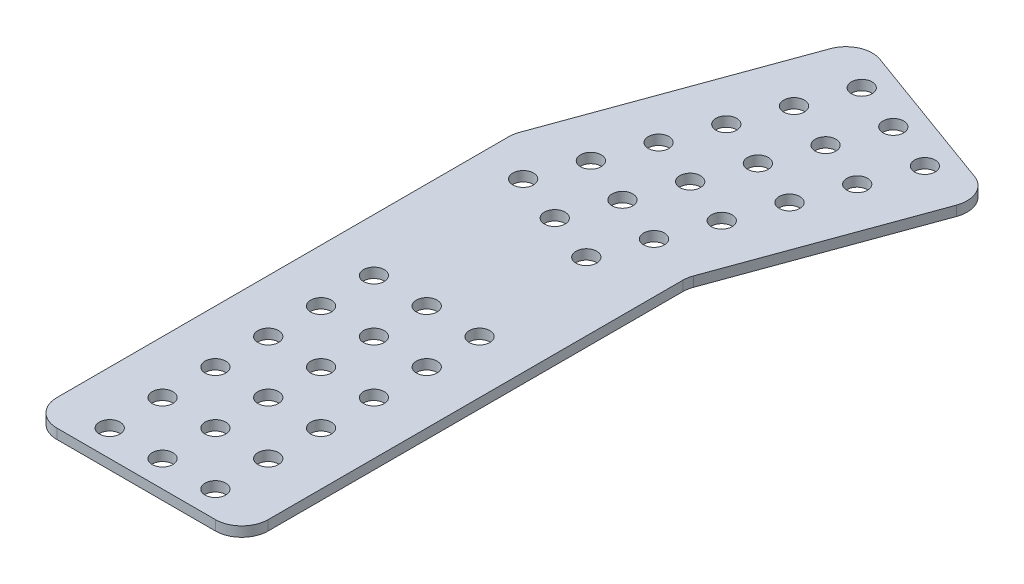
SolidWorks part; units mm, degrees
ref_plane "Front Plane" through (0, 0, 0) normal (0, 0, 1) x (1, 0, 0)
ref_plane "Top Plane" through (0, 0, 0) normal (0, 1, 0) x (1, 0, 0)
ref_plane "Right Plane" through (0, 0, 0) normal (1, 0, 0) x (0, 0, -1)
sketch "Sketch1" plane through (0, 0, 0) normal (0, 1, 0) x (1, 0, 0)
  line L0 (-80.3795, -295.1056) -> (-128.1159, -277.731) construction
  line L1 (-80.3795, -295.1056) -> (128.1159, 277.731) construction
  line L2 (-124.5455, -267.9214) -> (80.3795, 295.1056) construction
  line L3 (128.1159, 277.731) -> (80.3795, 295.1056) construction
  line L4 (-80.3795, -295.1056) -> (80.3795, 295.1056) construction
  line L5 (-128.1159, -277.731) -> (128.1159, 277.731) construction
  line L6 (104.2477, 286.4183) -> (-104.2477, -286.4183) construction
  line L7 (-73.7455, -307.8056) -> (-124.5455, -307.8056)
  line L8 (-73.7455, -307.8056) -> (-73.7455, -422.1056) construction
  line L9 (-73.7455, -422.1056) -> (-124.5455, -422.1056) construction
  line L10 (-124.5455, -307.8056) -> (-124.5455, -422.1056) construction
  line L11 (-99.1455, -307.8056) -> (-99.1455, -422.1056) construction
  line L12 (-105.4955, -307.8056) -> (-105.4955, -422.1056) construction
  line L13 (-99.1455, -307.8056) -> (-99.1455, -288.2754) construction
  line L14 (98.2807, 288.5901) -> (-110.2148, -284.2465) construction
  line L15 (-102.054, -206.1264) -> (-54.3176, -223.501)
  line L16 (-102.054, -206.1264) -> (-124.5455, -267.9214)
  line L19 (-73.7455, -384.0056) -> (-124.5455, -384.0056)
  line L20 (-73.7455, -307.8056) -> (-73.7455, -384.0056)
  line L21 (-124.5455, -307.8056) -> (-124.5455, -384.0056)
  line L22 (-124.5455, -307.8056) -> (-124.5455, -267.9214)
  line L23 (-124.5455, -267.9214) -> (-73.7455, -286.4111)
  line L24 (-73.7455, -307.8056) -> (-73.7455, -286.4111)
  line L26 (-128.1159, -277.731) -> (-124.5455, -307.8056) construction
  line L27 (-73.7455, -286.4111) -> (-73.7455, -276.8788)
  line L28 (-54.3176, -223.501) -> (-73.7455, -276.8788)
  circle A0 centre (-111.8455, -314.1556) radius 2.4892
  circle A1 centre (-111.8455, -326.8556) radius 2.4892
  circle A2 centre (-111.8455, -339.5556) radius 2.4892
  circle A3 centre (-111.8455, -352.2556) radius 2.4892
  circle A4 centre (-111.8455, -364.9556) radius 2.4892
  circle A5 centre (-111.8455, -377.6556) radius 2.4892
  circle A6 centre (-111.8455, -390.3556) radius 2.4892 construction
  circle A7 centre (-111.8455, -403.0556) radius 2.4892 construction
  circle A8 centre (-111.8455, -415.7556) radius 2.4892 construction
  circle A9 centre (-99.1455, -403.0556) radius 2.4892 construction
  circle A10 centre (-99.1455, -390.3556) radius 2.4892 construction
  circle A11 centre (-99.1455, -377.6556) radius 2.4892
  circle A12 centre (-99.1455, -364.9556) radius 2.4892
  circle A13 centre (-99.1455, -352.2556) radius 2.4892
  circle A14 centre (-99.1455, -339.5556) radius 2.4892
  circle A15 centre (-99.1455, -326.8556) radius 2.4892
  circle A16 centre (-99.1455, -314.1556) radius 2.4892
  circle A17 centre (-86.4455, -415.7556) radius 2.4892 construction
  circle A18 centre (-86.4455, -403.0556) radius 2.4892 construction
  circle A19 centre (-86.4455, -390.3556) radius 2.4892 construction
  circle A20 centre (-86.4455, -377.6556) radius 2.4892
  circle A21 centre (-86.4455, -364.9556) radius 2.4892
  circle A22 centre (-86.4455, -352.2556) radius 2.4892
  circle A23 centre (-86.4455, -339.5556) radius 2.4892
  circle A24 centre (-86.4455, -326.8556) radius 2.4892
  circle A25 centre (-86.4455, -314.1556) radius 2.4892
  circle A26 centre (-99.1455, -415.7556) radius 2.4892 construction
  circle A27 centre (90.1418, 284.7949) radius 2.4892 construction
  circle A28 centre (85.7982, 272.8608) radius 2.4892 construction
  circle A29 centre (81.4545, 260.9267) radius 2.4892 construction
  circle A30 centre (77.1108, 248.9926) radius 2.4892 construction
  circle A31 centre (72.7672, 237.0585) radius 2.4892 construction
  circle A32 centre (68.4235, 225.1244) radius 2.4892 construction
  circle A33 centre (64.0799, 213.1903) radius 2.4892 construction
  circle A34 centre (59.7362, 201.2562) radius 2.4892 construction
  circle A35 centre (55.3926, 189.3221) radius 2.4892 construction
  circle A36 centre (51.0489, 177.3881) radius 2.4892 construction
  circle A37 centre (46.7053, 165.454) radius 2.4892 construction
  circle A38 centre (42.3616, 153.5199) radius 2.4892 construction
  circle A39 centre (38.0179, 141.5858) radius 2.4892 construction
  circle A40 centre (33.6743, 129.6517) radius 2.4892 construction
  circle A41 centre (29.3306, 117.7176) radius 2.4892 construction
  circle A42 centre (24.987, 105.7835) radius 2.4892 construction
  circle A43 centre (20.6433, 93.8494) radius 2.4892 construction
  circle A44 centre (16.2997, 81.9153) radius 2.4892 construction
  circle A45 centre (11.956, 69.9812) radius 2.4892 construction
  circle A46 centre (7.6124, 58.0471) radius 2.4892 construction
  circle A47 centre (3.2687, 46.113) radius 2.4892 construction
  circle A48 centre (-1.075, 34.1789) radius 2.4892 construction
  circle A49 centre (-5.4186, 22.2448) radius 2.4892 construction
  circle A50 centre (-9.7623, 10.3107) radius 2.4892 construction
  circle A51 centre (-14.1059, -1.6234) radius 2.4892 construction
  circle A52 centre (-18.4496, -13.5575) radius 2.4892 construction
  circle A53 centre (-22.7932, -25.4916) radius 2.4892 construction
  circle A54 centre (-27.1369, -37.4257) radius 2.4892 construction
  circle A55 centre (-31.4805, -49.3598) radius 2.4892 construction
  circle A56 centre (-35.8242, -61.2939) radius 2.4892 construction
  circle A57 centre (-40.1679, -73.228) radius 2.4892 construction
  circle A58 centre (-44.5115, -85.1621) radius 2.4892 construction
  circle A59 centre (-48.8552, -97.0962) radius 2.4892 construction
  circle A60 centre (-53.1988, -109.0303) radius 2.4892 construction
  circle A61 centre (-57.5425, -120.9644) radius 2.4892 construction
  circle A62 centre (-61.8861, -132.8985) radius 2.4892 construction
  circle A63 centre (-66.2298, -144.8325) radius 2.4892 construction
  circle A64 centre (-70.5734, -156.7666) radius 2.4892 construction
  circle A65 centre (-74.9171, -168.7007) radius 2.4892 construction
  circle A66 centre (-79.2608, -180.6348) radius 2.4892 construction
  circle A67 centre (-83.6044, -192.5689) radius 2.4892 construction
  circle A68 centre (-87.9481, -204.503) radius 2.4892 construction
  circle A69 centre (-92.2917, -216.4371) radius 2.4892
  circle A70 centre (-96.6354, -228.3712) radius 2.4892
  circle A71 centre (-100.979, -240.3053) radius 2.4892
  circle A72 centre (-105.3227, -252.2394) radius 2.4892
  circle A73 centre (-109.6664, -264.1735) radius 2.4892
  circle A74 centre (-114.01, -276.1076) radius 2.4892
  circle A75 centre (62.983, 173.0444) radius 2.4892 construction
  circle A76 centre (67.3267, 184.9785) radius 2.4892 construction
  circle A77 centre (71.6703, 196.9126) radius 2.4892 construction
  circle A78 centre (76.014, 208.8467) radius 2.4892 construction
  circle A79 centre (80.3576, 220.7808) radius 2.4892 construction
  circle A80 centre (84.7013, 232.7149) radius 2.4892 construction
  circle A81 centre (89.0449, 244.649) radius 2.4892 construction
  circle A82 centre (93.3886, 256.5831) radius 2.4892 construction
  circle A83 centre (97.7323, 268.5172) radius 2.4892 construction
  circle A84 centre (102.0759, 280.4513) radius 2.4892 construction
  circle A85 centre (-102.0759, -280.4513) radius 2.4892
  circle A86 centre (-97.7323, -268.5172) radius 2.4892
  circle A87 centre (-93.3886, -256.5831) radius 2.4892
  circle A88 centre (-89.0449, -244.649) radius 2.4892
  circle A89 centre (-84.7013, -232.7149) radius 2.4892
  circle A90 centre (-80.3576, -220.7808) radius 2.4892
  circle A91 centre (-76.014, -208.8467) radius 2.4892 construction
  circle A92 centre (-71.6703, -196.9126) radius 2.4892 construction
  circle A93 centre (-67.3267, -184.9785) radius 2.4892 construction
  circle A94 centre (-62.983, -173.0444) radius 2.4892 construction
  circle A95 centre (-58.6394, -161.1103) radius 2.4892 construction
  circle A96 centre (-54.2957, -149.1762) radius 2.4892 construction
  circle A97 centre (-49.952, -137.2421) radius 2.4892 construction
  circle A98 centre (-45.6084, -125.308) radius 2.4892 construction
  circle A99 centre (-41.2647, -113.3739) radius 2.4892 construction
  circle A100 centre (-36.9211, -101.4398) radius 2.4892 construction
  circle A101 centre (-32.5774, -89.5057) radius 2.4892 construction
  circle A102 centre (-28.2338, -77.5716) radius 2.4892 construction
  circle A103 centre (-23.8901, -65.6375) radius 2.4892 construction
  circle A104 centre (-19.5465, -53.7034) radius 2.4892 construction
  circle A105 centre (-15.2028, -41.7693) radius 2.4892 construction
  circle A106 centre (-10.8591, -29.8352) radius 2.4892 construction
  circle A107 centre (-6.5155, -17.9011) radius 2.4892 construction
  circle A108 centre (-2.1718, -5.967) radius 2.4892 construction
  circle A109 centre (2.1718, 5.967) radius 2.4892 construction
  circle A110 centre (6.5155, 17.9011) radius 2.4892 construction
  circle A111 centre (10.8591, 29.8352) radius 2.4892 construction
  circle A112 centre (15.2028, 41.7693) radius 2.4892 construction
  circle A113 centre (19.5465, 53.7034) radius 2.4892 construction
  circle A114 centre (23.8901, 65.6375) radius 2.4892 construction
  circle A115 centre (28.2338, 77.5716) radius 2.4892 construction
  circle A116 centre (32.5774, 89.5057) radius 2.4892 construction
  circle A117 centre (36.9211, 101.4398) radius 2.4892 construction
  circle A118 centre (41.2647, 113.3739) radius 2.4892 construction
  circle A119 centre (45.6084, 125.308) radius 2.4892 construction
  circle A120 centre (49.952, 137.2421) radius 2.4892 construction
  circle A121 centre (54.2957, 149.1762) radius 2.4892 construction
  circle A122 centre (58.6394, 161.1103) radius 2.4892 construction
  circle A123 centre (-90.1418, -284.7949) radius 2.4892
  circle A124 centre (-85.7982, -272.8608) radius 2.4892
  circle A125 centre (-81.4545, -260.9267) radius 2.4892
  circle A126 centre (-77.1108, -248.9926) radius 2.4892
  circle A127 centre (-72.7672, -237.0585) radius 2.4892
  circle A128 centre (-68.4235, -225.1244) radius 2.4892
  circle A129 centre (-64.0799, -213.1903) radius 2.4892 construction
  circle A130 centre (-59.7362, -201.2562) radius 2.4892 construction
  circle A131 centre (-55.3926, -189.3221) radius 2.4892 construction
  circle A132 centre (-51.0489, -177.3881) radius 2.4892 construction
  circle A133 centre (-46.7053, -165.454) radius 2.4892 construction
  circle A134 centre (-42.3616, -153.5199) radius 2.4892 construction
  circle A135 centre (-38.0179, -141.5858) radius 2.4892 construction
  circle A136 centre (-33.6743, -129.6517) radius 2.4892 construction
  circle A137 centre (-29.3306, -117.7176) radius 2.4892 construction
  circle A138 centre (-24.987, -105.7835) radius 2.4892 construction
  circle A139 centre (-20.6433, -93.8494) radius 2.4892 construction
  circle A140 centre (-16.2997, -81.9153) radius 2.4892 construction
  circle A141 centre (-11.956, -69.9812) radius 2.4892 construction
  circle A142 centre (-7.6124, -58.0471) radius 2.4892 construction
  circle A143 centre (-3.2687, -46.113) radius 2.4892 construction
  circle A144 centre (1.075, -34.1789) radius 2.4892 construction
  circle A145 centre (5.4186, -22.2448) radius 2.4892 construction
  circle A146 centre (9.7623, -10.3107) radius 2.4892 construction
  circle A147 centre (14.1059, 1.6234) radius 2.4892 construction
  circle A148 centre (18.4496, 13.5575) radius 2.4892 construction
  circle A149 centre (22.7932, 25.4916) radius 2.4892 construction
  circle A150 centre (27.1369, 37.4257) radius 2.4892 construction
  circle A151 centre (31.4805, 49.3598) radius 2.4892 construction
  circle A152 centre (35.8242, 61.2939) radius 2.4892 construction
  circle A153 centre (40.1679, 73.228) radius 2.4892 construction
  circle A154 centre (44.5115, 85.1621) radius 2.4892 construction
  circle A155 centre (48.8552, 97.0962) radius 2.4892 construction
  circle A156 centre (53.1988, 109.0303) radius 2.4892 construction
  circle A157 centre (57.5425, 120.9644) radius 2.4892 construction
  circle A158 centre (61.8861, 132.8985) radius 2.4892 construction
  circle A159 centre (66.2298, 144.8325) radius 2.4892 construction
  circle A160 centre (70.5734, 156.7666) radius 2.4892 construction
  circle A161 centre (74.9171, 168.7007) radius 2.4892 construction
  circle A162 centre (79.2608, 180.6348) radius 2.4892 construction
  circle A163 centre (83.6044, 192.5689) radius 2.4892 construction
  circle A164 centre (87.9481, 204.503) radius 2.4892 construction
  circle A165 centre (92.2917, 216.4371) radius 2.4892 construction
  circle A166 centre (96.6354, 228.3712) radius 2.4892 construction
  circle A167 centre (100.979, 240.3053) radius 2.4892 construction
  circle A168 centre (105.3227, 252.2394) radius 2.4892 construction
  circle A169 centre (109.6664, 264.1735) radius 2.4892 construction
  circle A170 centre (114.01, 276.1076) radius 2.4892 construction
  point P1 (0, 0)
  dimension "D9" = 4.9784
  dimension "D15" = 4.9784
  dimension "D1" = 50.8
  dimension "D2" = 609.6
  dimension "D3" = 50.8
  dimension "D4" = 114.3
  dimension "D5" = 20
  dimension "D6" = 12.7
  dimension "D7" = 30.2858
  dimension "D8" = 6.35
  dimension "D10" = 6.35
  dimension "D11" = 12.7
  dimension "D13" = 12.7
  dimension "D14" = 6.35
  dimension "D16" = 6.35
  dimension "D17" = 12.7
  dimension "D19" = 12.7
  dimension "D20" = 6.35
  dimension "D21" = 6.35
  dimension "D12" = 9
  dimension "D18" = 48
extrude "Boss-Extrude1" add sketch "Sketch1" along normal blind 2.3813 contours L7 L21 L19 L20 A24 A22 A20 A15 A13 A11 A5 A4 A3 A2 A1 A0 A12 A14 A16 A21 A23 A25 | L7 L24 L23 L22 A85 A74 A123 | L23 L15 L16 A127 A125 A90 A88 A86 A73 A72 A71 A70 A69 A87 A89 A124 A126 A128 region at (-99.1455, 0, 345.9056) region at (-101.6855, 0, 292.472) region at (-98.7807, 0, 276.1639)
fillet "Fillet1" radius 6.35 6 edges at (-54.3176, 1.1906, 223.501) (-102.054, 1.1906, 206.1264) (-124.5455, 1.1906, 267.9214) (-73.7455, 1.1906, 276.8788) (-73.7455, 1.1906, 384.0056) (-124.5455, 1.1906, 384.0056)
